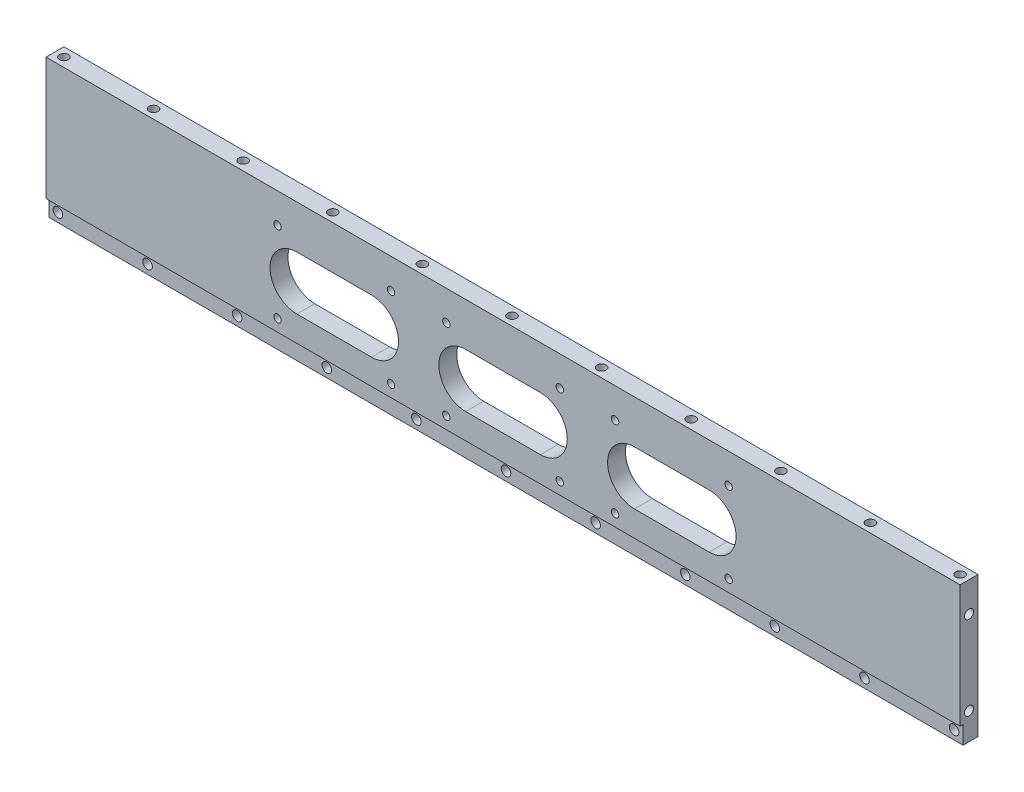
SolidWorks part; units mm, degrees
material "3.1325 (EN-AW 2017A)"
ref_plane "正面" through (0, 0, 0) normal (0, 0, 1) x (1, 0, 0)
ref_plane "平面" through (0, 0, 0) normal (0, 1, 0) x (1, 0, 0)
ref_plane "右側面" through (0, 0, 0) normal (1, 0, 0) x (0, 0, -1)
sketch "ｽｹｯﾁ1" plane through (0, 0, 0) normal (0, 0, 1) x (1, 0, 0)
  line L0 (0, 0) -> (109346.7417, 0) construction
  line L1 (0, 0) -> (0, -109346.7417) construction
  line L2 (-153, -17.5) -> (153, -17.5)
  line L3 (-153, -23.5) -> (153, -23.5)
  line L4 (-153, -23.5) -> (-153, 23.5)
  line L5 (-153, 23.5) -> (153, 23.5)
  line L6 (153, -23.5) -> (153, 23.5)
  point P11 (0, 13.5)
  point P13 (0, -14.5)
  point P19 (-150, -20.5)
  dimension "D1" = 47
  dimension "D2" = 306
  dimension "D3" = 6
  dimension "D7" = 28
  dimension "D8" = 10
  dimension "D4" = 3
  dimension "D5" = 300
extrude "ﾎﾞｽ - 押し出し1" add sketch "ｽｹｯﾁ1" along normal mid plane 6 contours L3 L6 L5 L4
extrude "ｶｯﾄ - 押し出し1" cut sketch "ｽｹｯﾁ1<4>" against normal blind 1 from surface contours L3 L6 L2 L4 region at (0, -20.5, 0) starting at face at (0, 0, 3)
sketch "ｽｹｯﾁ1<4>" plane through (0, 0, 0) normal (0, 0, 1) x (1, 0, 0) same geometry as "ｽｹｯﾁ1"
hole_wizard "M3 すきま穴1" positions "3Dｽｹｯﾁ1" profile "ｽｹｯﾁ2" hole size "M3" standard "JIS"
sketch3d "3Dｽｹｯﾁ1"
  point P10 (-150, -20.5, -3)
sketch "ｽｹｯﾁ2" plane through (-150, -20.5, -3) normal (1, 0, 0) x (0, 1, 0)
  line L0 (0, 0) -> (0, 6.9614)
  line L1 (0, 6.9614) -> (1.6, 6)
  line L2 (1.6, 6) -> (1.6, 0)
  line L5 (1.6, 0) -> (0, 0)
  line L10 (0, 6.9614) -> (-1.6, 6) construction
  line L11 (0, -6.35) -> (0, 107.95) construction
  dimension "穴の直径" = 3.2
  dimension "穴の深さ" = 6
  dimension "ﾄﾞﾘﾙ角度" = 118
hole_wizard "M3x0.5 ねじ穴3" positions "3Dｽｹｯﾁ2" profile "ｽｹｯﾁ3" tap size "M3x0.5" standard "JIS"
sketch3d "3Dｽｹｯﾁ2"
  point P0 (-153, 13.5, 0)
  point P2 (-153, -14.5, 0)
  point P4 (153, 13.5, 0)
  point P6 (153, -14.5, 0)
sketch "ｽｹｯﾁ3" plane through (-153, 13.5, 0) normal (0, 1, 0) x (0, 0, 1)
  line L0 (0, 0) -> (0, 9.2511)
  line L1 (0, 9.2511) -> (1.25, 8.5)
  line L2 (1.25, 8.5) -> (1.25, 6)
  line L3 (1.25, 6) -> (1.5, 6)
  line L4 (1.5, 6) -> (1.5, 0)
  line L5 (1.5, 0) -> (0, 0)
  line L10 (0, 9.2511) -> (-1.25, 8.5) construction
  line L11 (0, -6.35) -> (0, 107.95) construction
  dimension "ねじ下穴ﾄﾞﾘﾙ直径" = 2.5
  dimension "ねじ下穴ﾄﾞﾘﾙの深さ" = 8.5
  dimension "ねじ山の主要直径" = 3
  dimension "ねじ山の深さ" = 6
  dimension "ﾄﾞﾘﾙ角度" = 118
hole_wizard "M3x0.5 ねじ穴2" positions "3Dｽｹｯﾁ5" profile "ｽｹｯﾁ6" tap size "M3x0.5" standard "JIS"
sketch3d "3Dｽｹｯﾁ5"
  point P10 (-150, 23.5, 0)
sketch "ｽｹｯﾁ6" plane through (-150, 23.5, 0) normal (1, 0, 0) x (0, 0, 1)
  line L0 (0, 0) -> (0, 9.2511)
  line L1 (0, 9.2511) -> (1.25, 8.5)
  line L2 (1.25, 8.5) -> (1.25, 6)
  line L3 (1.25, 6) -> (1.5, 6)
  line L4 (1.5, 6) -> (1.5, 0)
  line L5 (1.5, 0) -> (0, 0)
  line L10 (0, 9.2511) -> (-1.25, 8.5) construction
  line L11 (0, -6.35) -> (0, 107.95) construction
  dimension "ねじ下穴ﾄﾞﾘﾙ直径" = 2.5
  dimension "ねじ下穴ﾄﾞﾘﾙの深さ" = 8.5
  dimension "ねじ山の主要直径" = 3
  dimension "ねじ山の深さ" = 6
  dimension "ﾄﾞﾘﾙ角度" = 118
pattern_linear "直線ﾊﾟﾀｰﾝ1" count 11 spacing 30 along (1, 0, 0) of "M3x0.5 ねじ穴2", "M3 すきま穴1"
sketch "ｽｹｯﾁ7" plane through (0, 0, -3) normal (0, 0, -1) x (-1, 0, 0)
  line L0 (37.5, 13.5) -> (75.5, 13.5) construction
  line L1 (37.5, 13.5) -> (37.5, -13.5) construction
  line L2 (75.5, 13.5) -> (75.5, -13.5) construction
  line L3 (37.5, -13.5) -> (75.5, -13.5) construction
  line L4 (-19, 13.5) -> (19, 13.5) construction
  line L5 (-19, 13.5) -> (-19, -13.5) construction
  line L6 (19, 13.5) -> (19, -13.5) construction
  line L7 (-19, -13.5) -> (19, -13.5) construction
  line L8 (-75.5, 13.5) -> (-37.5, 13.5) construction
  line L9 (-75.5, 13.5) -> (-75.5, -13.5) construction
  line L10 (-37.5, 13.5) -> (-37.5, -13.5) construction
  line L11 (-75.5, -13.5) -> (-37.5, -13.5) construction
  line L14 (-37.5, 0) -> (37.5, 0) construction
  line L15 (69, 0) -> (44, 0) construction
  line L16 (69, -9) -> (44, -9)
  line L17 (69, 9) -> (44, 9)
  line L18 (12.5, 0) -> (-12.5, 0) construction
  line L19 (12.5, -9) -> (-12.5, -9)
  line L20 (12.5, 9) -> (-12.5, 9)
  line L21 (-44, 0) -> (-69, 0) construction
  line L22 (-44, -9) -> (-69, -9)
  line L23 (-44, 9) -> (-69, 9)
  line L24 (56.5, 9) -> (56.5, -0.221) construction
  line L25 (-56.5, 0) -> (-56.5, 13.5) construction
  circle A0 centre (37.5, 13.5) radius 1.25
  circle A1 centre (75.5, 13.5) radius 1.25
  circle A2 centre (37.5, -13.5) radius 1.25
  circle A3 centre (75.5, -13.5) radius 1.25
  circle A4 centre (-19, 13.5) radius 1.25
  circle A5 centre (19, 13.5) radius 1.25
  circle A6 centre (-19, -13.5) radius 1.25
  circle A7 centre (19, -13.5) radius 1.25
  circle A8 centre (-75.5, 13.5) radius 1.25
  circle A9 centre (-37.5, 13.5) radius 1.25
  circle A10 centre (-75.5, -13.5) radius 1.25
  circle A11 centre (-37.5, -13.5) radius 1.25
  arc A12 (69, -9) -> (69, 9) centre (69, 0) ccw
  arc A13 (44, 9) -> (44, -9) centre (44, 0) ccw
  arc A14 (12.5, -9) -> (12.5, 9) centre (12.5, 0) ccw
  arc A15 (-12.5, 9) -> (-12.5, -9) centre (-12.5, 0) ccw
  arc A16 (-44, -9) -> (-44, 9) centre (-44, 0) ccw
  arc A17 (-69, 9) -> (-69, -9) centre (-69, 0) ccw
  point P26 (75.5, 0)
  point P29 (19, 0)
  point P30 (-37.5, 0)
  point P32 (0, 0)
  point P33 (0, 13.5)
  point P35 (56.5, 0)
  point P43 (0, 0)
  point P50 (-56.5, 0)
  point P57 (56.5, 13.5)
  dimension "D1" = 2.5
  dimension "D4" = 2.5
  dimension "D7" = 2.5
  dimension "D13" = 9
  dimension "D15" = 9
  dimension "D17" = 9
  dimension "D2" = 38
  dimension "D3" = 27
  dimension "D5" = 38
  dimension "D6" = 27
  dimension "D8" = 38
  dimension "D9" = 27
  dimension "D10" = 75
  dimension "D11" = 27
  dimension "D12" = 25
  dimension "D14" = 25
  dimension "D16" = 25
extrude "ｶｯﾄ - 押し出し2" cut sketch "ｽｹｯﾁ7" against normal through all
equation "\"回路ボックス横幅\" = 316"
equation "\"D2@ｽｹｯﾁ1\" = \"回路ボックス横幅\" - 2 * ( \"回路ボックス板厚\" - \"接合溝\" )"
equation "\"回路ボックス板厚\"= 6"
equation "\"回路ボックス板接合ねじ間隔_横幅方向\"= 30"
equation "\"回路ボックス板接合ねじ個数_横幅方向\"= 11"
equation "\"回路ボックス板接合ねじ間隔_全長方向\"= 30"
equation "\"接合溝\"= 1"
equation "\"ミル径\"= 1"
equation "\"フリッパ駆動ユニット+床板取付け位置\"= 16"
equation "\"D3@直線ﾊﾟﾀｰﾝ1\"=\"回路ボックス板接合ねじ間隔_横幅方向\""
equation "\"D1@直線ﾊﾟﾀｰﾝ1\"=\"回路ボックス板接合ねじ個数_横幅方向\""
equation "\"D4@直線ﾊﾟﾀｰﾝ1\"=\"回路ボックス板接合ねじ間隔_横幅方向\""
equation "\"D5@ｽｹｯﾁ1\"=\"回路ボックス板接合ねじ間隔_横幅方向\"*(\"回路ボックス板接合ねじ個数_横幅方向\"-1)"
